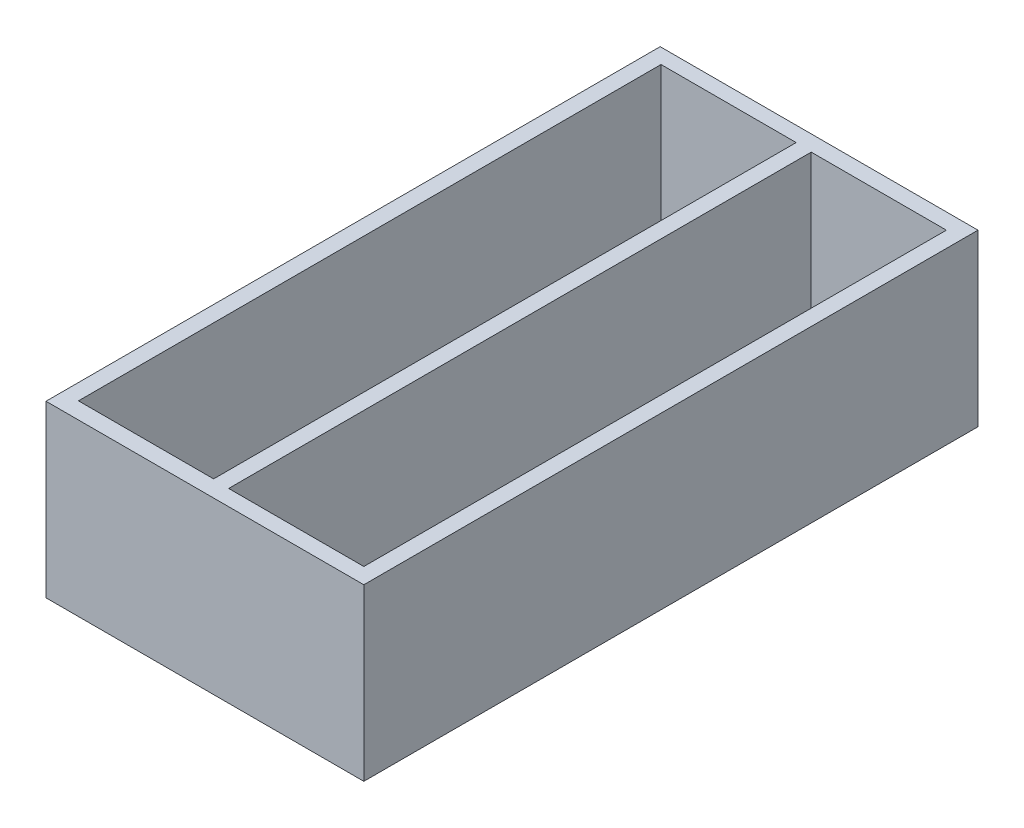
SolidWorks part; units mm, degrees
ref_plane "Front Plane" through (0, 0, 0) normal (0, 0, 1) x (1, 0, 0)
ref_plane "Top Plane" through (0, 0, 0) normal (0, 1, 0) x (1, 0, 0)
ref_plane "Right Plane" through (0, 0, 0) normal (1, 0, 0) x (0, 0, -1)
sketch "Sketch1" plane through (0, 0, 0) normal (0, 1, 0) x (1, 0, 0)
  line L1 (-27.7017, -18.3834) -> (12.5083, -18.3834)
  line L2 (-27.7017, -18.3834) -> (-27.7017, 59.3166)
  line L3 (-27.7017, 59.3166) -> (12.5083, 59.3166)
  line L4 (12.5083, -18.3834) -> (12.5083, 59.3166)
  dimension "D1" = 77.7
  dimension "D2" = 40.21
extrude "Boss-Extrude1" add sketch "Sketch1" along normal blind 21.54
sketch "Sketch2" plane through (0, 21.54, 0) normal (0, 1, 0) x (1, 0, 0)
  line L0 (12.5083, -18.3834) -> (12.5083, 59.3166) construction
  line L1 (10.5083, -16.3834) -> (-6.5917, -16.3834)
  line L2 (10.5083, -16.3834) -> (10.5083, 57.3166)
  line L3 (10.5083, 57.3166) -> (-6.5917, 57.3166)
  line L4 (-6.5917, -16.3834) -> (-6.5917, 57.3166)
  line L5 (12.5083, 59.3166) -> (-27.7017, 59.3166) construction
  line L6 (-8.5917, -16.2855) -> (-25.6917, -16.2855)
  line L7 (-8.5917, -16.2855) -> (-8.5917, 57.4145)
  line L8 (-8.5917, 57.4145) -> (-25.6917, 57.4145)
  line L9 (-25.6917, -16.2855) -> (-25.6917, 57.4145)
  dimension "D1" = 17.1
  dimension "D2" = 73.7
  dimension "D3" = 2
  dimension "D4" = 2
  dimension "D5" = 17.1
  dimension "D6" = 73.7
  dimension "D7" = 2
extrude "Cut-Extrude1" cut sketch "Sketch2" against normal blind 19.54
